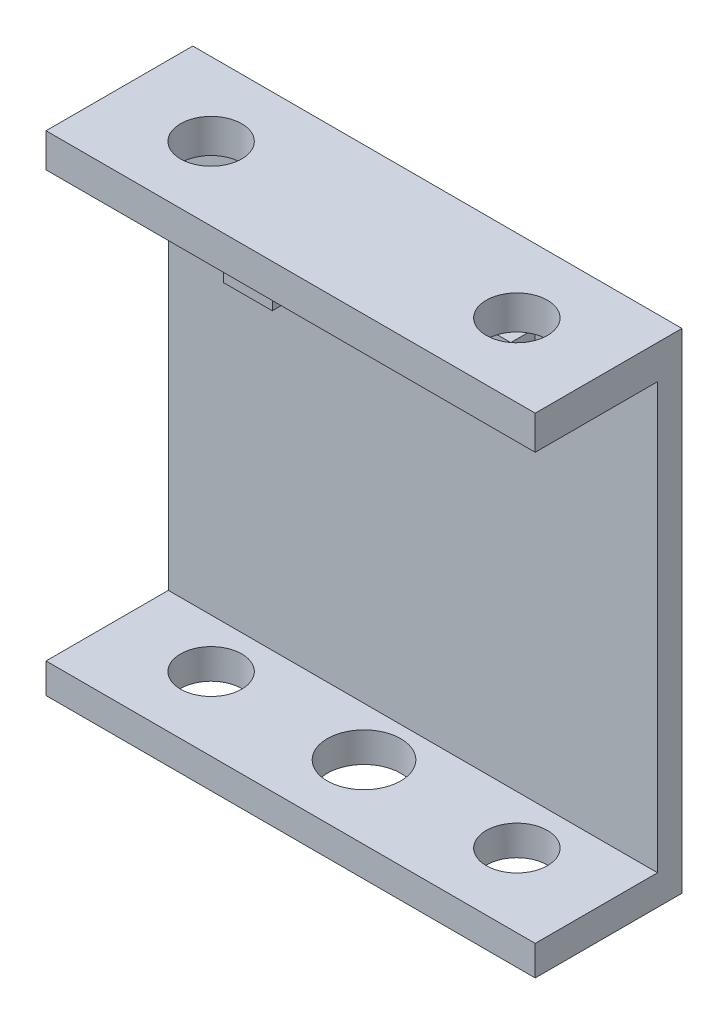
SolidWorks part; units mm, degrees
ref_plane "정면" through (0, 0, 0) normal (0, 0, 1) x (1, 0, 0)
ref_plane "윗면" through (0, 0, 0) normal (0, 1, 0) x (1, 0, 0)
ref_plane "우측면" through (0, 0, 0) normal (1, 0, 0) x (0, 0, -1)
sketch "스케치1" plane through (0, 0, 0) normal (0, 0, 1) x (1, 0, 0)
  line L0 (20, -7) -> (20, -10) construction
  line L1 (0, 0) -> (40, 0)
  line L2 (0, 0) -> (0, -40)
  line L3 (0, -40) -> (40, -40)
  line L4 (40, 0) -> (40, -40)
  line L5 (17, -10) -> (23, -10)
  line L6 (17, -10) -> (17, -31)
  line L7 (17, -31) -> (23, -31)
  line L8 (23, -10) -> (23, -31)
  line L9 (19, -10) -> (21, -10)
  line L10 (19, -10) -> (19, -7)
  line L11 (19, -7) -> (21, -7)
  line L12 (21, -10) -> (21, -7)
  line L13 (20, -10) -> (20, -40) construction
  line L14 (5, 5) -> (35, 5) construction
  line L15 (5, 5) -> (5, -10)
  line L16 (5, -10) -> (10, -10)
  line L17 (10, -10) -> (10, 5)
  line L18 (30, 5) -> (30, -35)
  line L19 (30, -35) -> (35, -35)
  line L20 (35, -35) -> (35, 5)
  line L22 (4, -4) -> (30, -4)
  line L23 (4, -4) -> (4, -8)
  line L24 (4, -8) -> (30, -8)
  line L25 (30, -4) -> (30, -8)
  line L26 (18, -4) -> (22, -4)
  line L27 (18, -4) -> (18, -9)
  line L28 (18, -9) -> (22, -9)
  line L29 (22, -4) -> (22, -9)
  arc A0 (10, 5) -> (30, 5) centre (20, 5) cw
  arc A1 (5, 5) -> (35, 5) centre (20, 5) cw
  point P30 (20, -9)
  dimension "D7" = 5
  dimension "D8" = 10
  dimension "D1" = 2
  dimension "D2" = 3
  dimension "D3" = 21
  dimension "D4" = 6
  dimension "D5" = 40
  dimension "D6" = 40
  dimension "D9" = 40
  dimension "D10" = 15
  dimension "D11" = 10
  dimension "D12" = 5
  dimension "D13" = 4
  dimension "D14" = 4
  dimension "D15" = 5
  dimension "D16" = 2
  dimension "D17" = 1
sketch "스케치2" plane through (0, 0, 0) normal (0, 0, 1) x (1, 0, 0)
  line L1 (0, 0) -> (40, 0)
  line L2 (0, 0) -> (0, -40)
  line L3 (0, -40) -> (40, -40)
  line L4 (40, 0) -> (40, -40)
extrude "보스-돌출1" add sketch "스케치2" along normal blind 12
sketch "스케치3" plane through (0, 0, 0) normal (0, 1, 0) x (1, 0, 0)
  line L0 (0, -6) -> (40, -6) construction
  line L1 (0, -12) -> (0, 0) construction
  line L2 (40, -12) -> (40, 0) construction
  circle A0 centre (7.5, -6) radius 2.5
  circle A1 centre (32.5, -6) radius 2.5
  point P10 (20, -6)
  dimension "D1" = 5
  dimension "D2" = 25
  dimension "D3" = 12.5
extrude "컷-돌출1" cut sketch "스케치3" against normal through all
sketch "스케치4" plane through (0, 0, 12) normal (0, 0, 1) x (1, 0, 0)
  line L0 (0, 0) -> (0, -40) construction
  line L1 (0, -2.7719) -> (40, -2.7719)
  line L2 (0, -2.7719) -> (0, -37.5472)
  line L3 (0, -37.5472) -> (40, -37.5472)
  line L4 (40, -2.7719) -> (40, -37.5472)
  line L5 (40, 0) -> (40, -40) construction
extrude "컷-돌출2" cut sketch "스케치4" against normal blind 10
sketch "스케치6" plane through (0, -40, 0) normal (0, -1, 0) x (1, 0, 0)
  line L0 (0, 6) -> (40, 6) construction
  line L1 (0, 12) -> (0, 0) construction
  line L2 (40, 12) -> (40, 0) construction
  circle A0 centre (20, 6) radius 3
  dimension "D1" = 6
extrude "컷-돌출3" cut sketch "스케치6" against normal blind 10
sketch "스케치7" plane through (0, 0, 2) normal (0, 0, 1) x (1, 0, 0)
  line L0 (4, -8) -> (30, -8) construction
  line L1 (30, -4) -> (26, -4)
  line L2 (30, -4) -> (30, -8)
  line L3 (30, -8) -> (26, -8)
  line L4 (26, -4) -> (26, -8)
  line L5 (4, -4) -> (30, -4) construction
  line L6 (14, -4) -> (10, -4)
  line L7 (14, -4) -> (14, -8)
  line L8 (14, -8) -> (10, -8)
  line L9 (10, -4) -> (10, -8)
  line L10 (10, -10) -> (10, 5) construction
  dimension "D1" = 4
  dimension "D2" = 4
extrude "보스-돌출2" add sketch "스케치7" along normal blind 2 contours L1 L4 L3 L2 region at (28, -6, 2)
extrude "보스-돌출3" add sketch "스케치7<3>" along normal blind 5.5 contours L6 L9 L8 L7 region at (12, -6, 2)
sketch "스케치7<3>" plane through (0, 0, 2) normal (0, 0, 1) x (1, 0, 0) same geometry as "스케치7"
